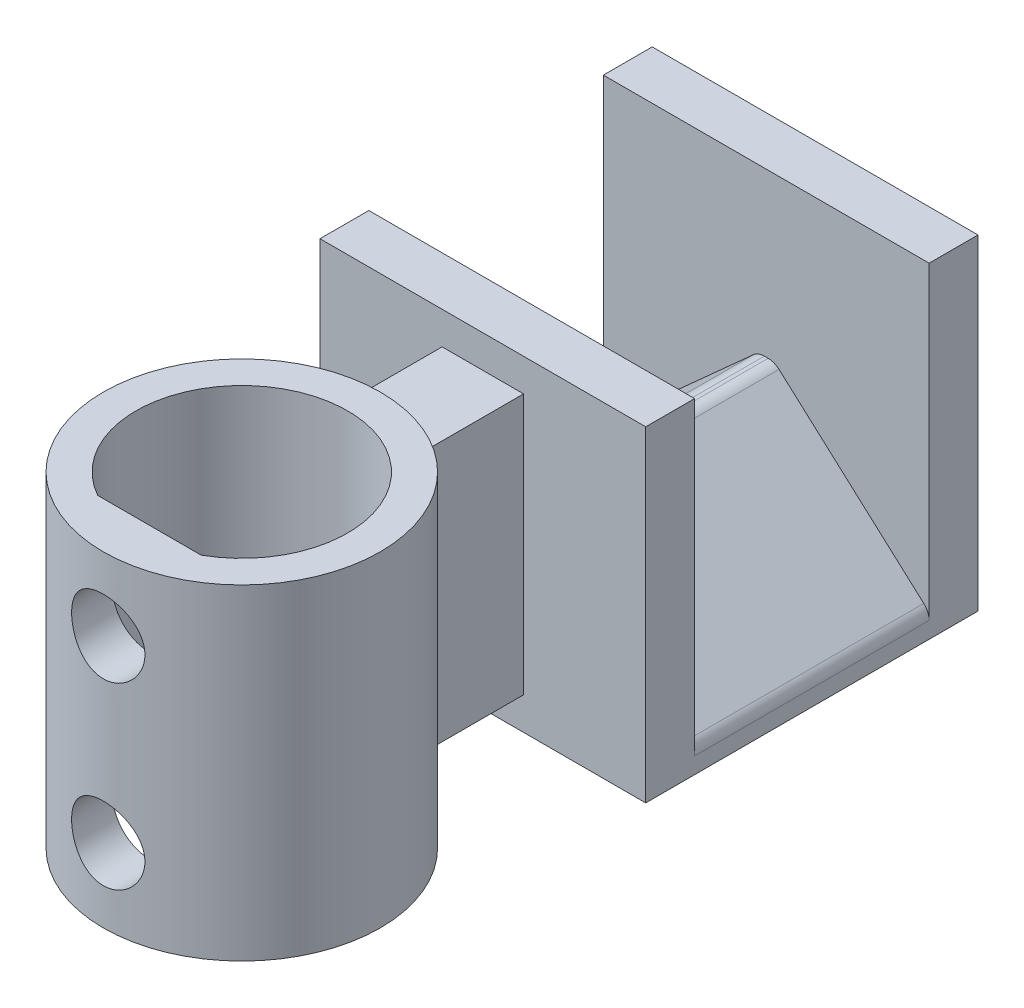
SolidWorks part; units mm, degrees
ref_plane "Front Plane" through (0, 0, 0) normal (0, 0, 1) x (1, 0, 0)
ref_plane "Top Plane" through (0, 0, 0) normal (0, 1, 0) x (1, 0, 0)
ref_plane "Right Plane" through (0, 0, 0) normal (1, 0, 0) x (0, 0, -1)
sketch "Sketch2" plane through (0, 0, 0) normal (0, 0, 1) x (1, 0, 0)
  line L1 (-10, -5) -> (10, -5)
  line L2 (-10, -5) -> (-10, 5)
  line L3 (-10, 5) -> (10, 5)
  line L4 (10, -5) -> (10, 5)
  line L5 (-10, -5) -> (10, 5) construction
  line L6 (-10, 5) -> (10, -5) construction
  point P0 (0, 0)
  dimension "D1" = 10
  dimension "D2" = 20
extrude "Boss-Extrude1" add sketch "Sketch2" along normal mid plane 14.4
chamfer "Chamfer1" distance 9.5 angle 42 2 edges at (10, 5, 0) (-10, 5, 0) first distance on face at (0, 5, 0)
fillet "Fillet3" radius 1 4 edges at (-10, -3.5538, 0) (10, -3.5538, 0) (0.5, 5, 0) (-0.5, 5, 0)
sketch "Sketch3" plane through (0, 0, 7.2) normal (0, 0, 1) x (1, 0, 0)
  line L0 (-10, -5) -> (10, -5) construction
  line L1 (-10, 15) -> (10, 15)
  line L2 (-10, 15) -> (-10, -5)
  line L3 (-10, -5) -> (10, -5)
  line L4 (10, 15) -> (10, -5)
  line L5 (-10, 15) -> (10, -5) construction
  line L6 (-10, -5) -> (10, 15) construction
  point P0 (0, 5)
  dimension "D1" = 20
  dimension "D2" = 20
extrude "Boss-Extrude2" add sketch "Sketch3" along normal blind 3
mirror "Mirror1" about plane through (0, 0, 0) normal (0, 0, 1) of "Boss-Extrude2"
sketch "Sketch6" plane through (0, 0, 0) normal (0, 1, 0) x (1, 0, 0)
  line L0 (3.175, -30.6718) -> (-3.175, -30.6718)
  arc A0 (3.175, -30.6718) -> (-3.175, -30.6718) centre (0, -25) ccw
  circle A1 centre (0, -25) radius 8.5
  dimension "D1" = 13
  dimension "D2" = 2
  dimension "D3" = 25
  dimension "D4" = 6.35
extrude "Boss-Extrude3" add sketch "Sketch6" along normal up to surface and the other way up to surface separate body up to face at (0, 15, 8.7) other way up to face at (0, -5, 0)
sketch "Sketch5" plane through (0, 0, 10.2) normal (0, 0, 1) x (1, 0, 0)
  line L0 (-10, -5) -> (10, -5) construction
  line L1 (-2.5, 13) -> (2.5, 13)
  line L2 (-2.5, 13) -> (-2.5, -3)
  line L3 (-2.5, -3) -> (2.5, -3)
  line L4 (2.5, 13) -> (2.5, -3)
  line L5 (-2.5, 13) -> (2.5, -3) construction
  line L6 (-2.5, -3) -> (2.5, 13) construction
  line L7 (10, 15) -> (-10, 15) construction
  point P0 (0, 5)
  dimension "D1" = 2
  dimension "D2" = 2
  dimension "D3" = 5
extrude "Boss-Extrude4" add sketch "Sketch5" along normal up to surface (6.676 mm away) up to face at (0, 15, 16.5)
ref_plane "Plane1" through (0, 0, 20) normal (0, 0, 1) x (1, 0, 0)
sketch "Sketch7" plane through (0, 0, 20) normal (0, 0, 1) x (1, 0, 0)
  line L0 (-8.5, -5) -> (8.5, -5) construction
  line L1 (6.5, 15) -> (-6.5, 15) construction
  circle A0 centre (0, 10.5) radius 2.25
  circle A1 centre (0, -0.5) radius 2.25
  dimension "D1" = 4.5
  dimension "D2" = 4.5
  dimension "D3" = 4.5
  dimension "D4" = 4.5
extrude "Cut-Extrude1" cut sketch "Sketch7" along normal up to surface (13.1968 mm away) up to face at (0, 15, 16.5)
